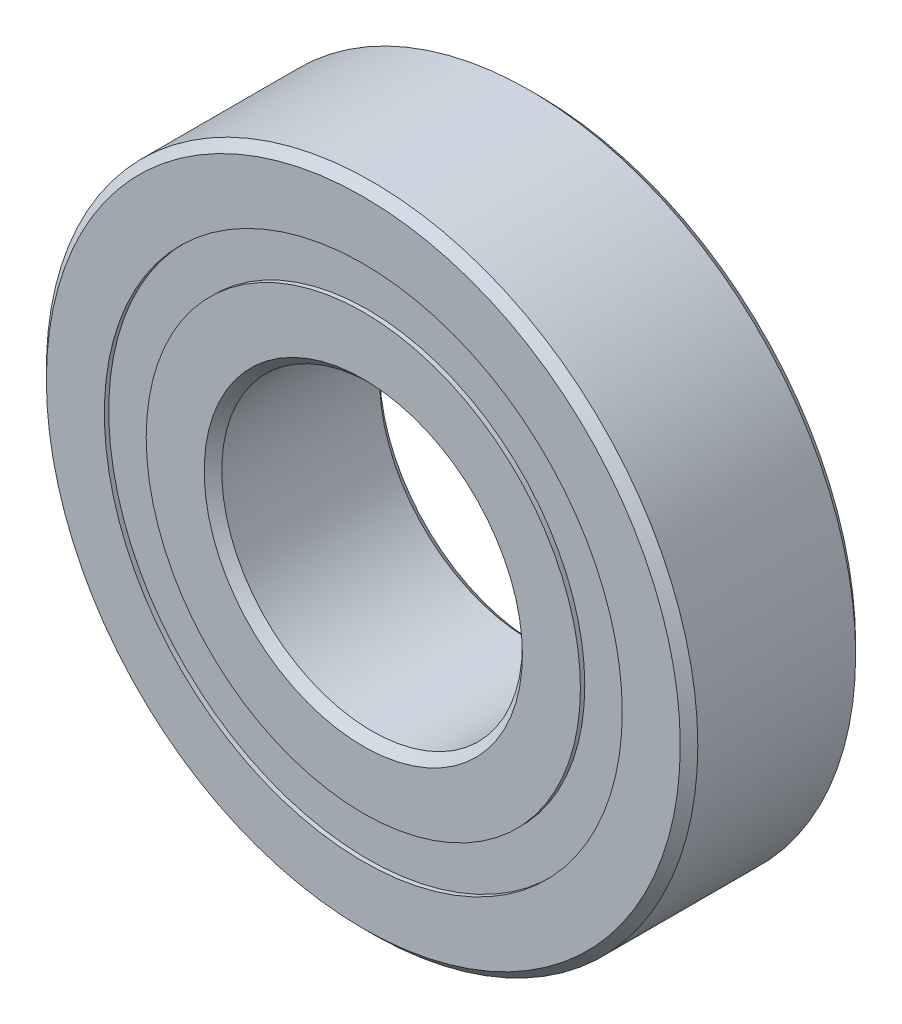
SolidWorks part; units mm, degrees
ref_plane "Front Plane" through (0, 0, 0) normal (0, 0, 1) x (1, 0, 0)
ref_plane "Top Plane" through (0, 0, 0) normal (0, 1, 0) x (1, 0, 0)
ref_plane "Right Plane" through (0, 0, 0) normal (1, 0, 0) x (0, 0, -1)
sketch "Sketch1" plane through (0, 0, 0) normal (1, 0, 0) x (0, 0, -1)
  line L0 (-5.5562, 0) -> (5.5562, 0) construction
  line L1 (0, 20.6375) -> (0, -20.6375) construction
  line L2 (5.0006, 20.6375) -> (-5.0006, 20.6375)
  line L3 (-5.0006, 20.6375) -> (-5.5563, 20.0819)
  line L4 (-5.5563, 20.0819) -> (-5.5563, 16.4071)
  line L5 (-5.5563, 16.4071) -> (-2.4694, 16.4071)
  line L6 (5.5563, 16.4071) -> (2.4694, 16.4071)
  line L7 (5.5563, 20.0819) -> (5.5563, 16.4071)
  line L8 (5.0006, 20.6375) -> (5.5563, 20.0819)
  line L9 (0, 20.6375) -> (0, 15.0813) construction
  line L10 (0, 15.0813) -> (0, 9.525) construction
  arc A0 (-2.4694, 16.4071) -> (2.4694, 16.4071) centre (0, 15.0813) cw
  point P14 (0, 9.525)
  dimension "D3" = 4.9389
  dimension "D1" = 45
  dimension "Width" = 11.1125
  dimension "OD" = 41.275
  dimension "D2" = 0.5556
  dimension "Shaft Dia" = 19.05
  dimension "D4" = 1.3258
revolve "Revolve1" add sketch "Sketch1" angle 360 about L0
sketch "Sketch3" plane through (0, 0, 0) normal (1, 0, 0) x (0, 0, -1)
  line L0 (-5.5563, 13.7554) -> (-2.4694, 13.7554)
  line L1 (0, 20.6375) -> (0, -20.6375) construction
  line L2 (-5.5563, 20.0819) -> (-5.5563, 16.4071) construction
  line L3 (-5.5563, 13.7554) -> (-5.5563, 10.0806)
  line L4 (-5.0006, 20.6375) -> (-5.5563, 20.0819) construction
  line L5 (-5.5563, 10.0806) -> (-5.0006, 9.525)
  line L6 (-5.0006, 9.525) -> (5.0006, 9.525)
  line L7 (5.0006, 20.6375) -> (5.0006, -20.6375) construction
  line L8 (5.0006, 9.525) -> (5.5563, 10.0806)
  line L9 (5.5563, -20.0819) -> (5.5563, 20.0819) construction
  line L10 (5.5563, 10.0806) -> (5.5563, 13.7554)
  line L11 (5.5563, 13.7554) -> (2.4694, 13.7554)
  line L13 (5.0006, 20.6375) -> (5.5563, 20.0819) construction
  arc A0 (2.4694, 16.4071) -> (-2.4694, 16.4071) centre (0, 15.0813) ccw construction
  arc A1 (2.4694, 13.7554) -> (-2.4694, 13.7554) centre (0, 15.0812) cw
revolve "Revolve3" add sketch "Sketch3" angle 360 about L0
sketch "Sketch4" plane through (0, 0, 0) normal (1, 0, 0) x (0, 0, -1)
  line L0 (-2.8028, 15.0813) -> (2.8028, 15.0813)
  arc A2 (-2.8028, 15.0813) -> (2.8028, 15.0813) centre (0, 15.0813) cw
  arc A3 (2.4694, 16.4071) -> (-2.4694, 16.4071) centre (0, 15.0813) ccw construction
revolve "Revolve4" add sketch "Sketch4" angle 360 about L0
ref_axis "Axis1" through (0, 0, -5.5562) along (0, 0, 1)
pattern_circular "CirPattern1" count 10 every 36 about axis through (0, 0, -5.5562) along (0, 0, 1) of bodies 104
sketch "Sketch5" plane through (0, 0, 0) normal (1, 0, 0) x (0, 0, -1)
  line L0 (-5.5563, 16.4071) -> (-2.4694, 16.4071) construction
  line L1 (-5.2784, 16.4071) -> (-2.8028, 16.4071)
  line L2 (-5.2784, 16.4071) -> (-5.2784, 13.7554)
  line L3 (-5.2784, 13.7554) -> (-2.8028, 13.7554)
  line L4 (-2.8028, 16.4071) -> (-2.8028, 13.7554)
  line L5 (-5.5563, 13.7554) -> (-2.4694, 13.7554) construction
  line L6 (5.5563, 16.4071) -> (2.4694, 16.4071) construction
  line L7 (5.2784, 16.4071) -> (2.8028, 16.4071)
  line L8 (5.2784, 16.4071) -> (5.2784, 13.7554)
  line L9 (5.2784, 13.7554) -> (2.8028, 13.7554)
  line L10 (2.8028, 16.4071) -> (2.8028, 13.7554)
  line L11 (5.5563, 13.7554) -> (2.4694, 13.7554) construction
  line L12 (-5.0006, 20.6375) -> (-5.5563, 20.0819) construction
  point P18 (-5.2784, 20.3597)
revolve "Revolve5" add sketch "Sketch5" angle 360 about L0
equation "\"D2@Sketch1\" = \"Width@Sketch1\"*.05"
equation "\"D3@Sketch1\" = \"Width@Sketch1\"/2.25"
equation "\"D4@Sketch1\" = (((\"OD@Sketch1\"-\"Width@Sketch1\")/2)/3.25)/3.5"
equation "\"D2@CirPattern1\" = 360/\"Balls@CirPattern1\""
